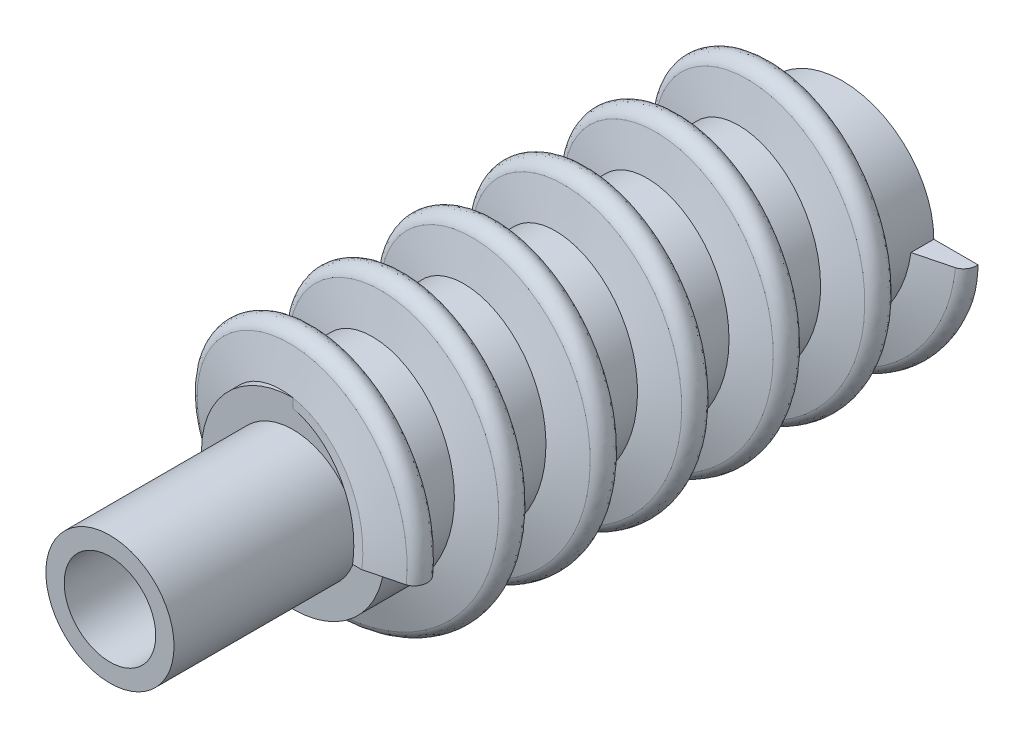
SolidWorks part; units mm, degrees
ref_plane "Front Plane" through (0, 0, 0) normal (0, 0, 1) x (1, 0, 0)
ref_plane "Top Plane" through (0, 0, 0) normal (0, 1, 0) x (1, 0, 0)
ref_plane "Right Plane" through (0, 0, 0) normal (1, 0, 0) x (0, 0, -1)
sketch "Sketch1" plane through (0, 0, 0) normal (0, 0, 1) x (1, 0, 0)
  circle A0 centre (0, 0) radius 5
  dimension "D1" = 10
extrude "Boss-Extrude1" add sketch "Sketch1" along normal blind 30
sketch "Sketch2" plane through (0, 0, 30) normal (0, 0, 1) x (1, 0, 0)
  circle A0 centre (0, 0) radius 3.5
  circle A1 centre (0, 0) radius 2.5
  dimension "D1" = 1
extrude "Boss-Extrude2" add sketch "Sketch2" along normal blind 10
sketch "Sketch5" plane through (0, 0, 0) normal (0, 0, 1) x (1, 0, 0)
  circle A0 centre (0, 0) radius 5 construction
  circle A1 centre (0, 0) radius 5
curve "Helix/Spiral1" pitch 5 height 30 radius 5 left hand yes centre (0, 0, 0) axis (0, 0, 1) start towards (1, 0, 0)
sketch "Sketch7" plane through (0, 0, 0) normal (1, 0, 0) x (0, 0, -1)
  line L12 (0, 5) -> (-30, 5) construction
  line L13 (-27.5, 5) -> (-27.5, 4.5)
  line L15 (-27.5, 4.5) -> (-30, 4.5)
  line L16 (-30, 5) -> (-30, -5) construction
  line L17 (-30, 4.5) -> (-30, 5)
  line L19 (-27.5, 5) -> (-28.1504, 6.8913)
  line L21 (-29.5038, 6.9375) -> (-30, 5)
  arc A1 (-29.5038, 6.9375) -> (-28.1504, 6.8913) centre (-28.8341, 6.7107) cw
  dimension "D1" = 2.5
  dimension "D2" = 0.5
sweep "Sweep2" add profiles "Sketch7" path "Helix/Spiral1"
sketch "Sketch36" plane through (0, 0, 0) normal (0, 1, 0) x (1, 0, 0)
  line L0 (11.1386, 0) -> (-5, 0)
  line L4 (11.1386, 0) -> (11.1386, 1.4522)
  line L6 (-5, 0) -> (-5, 1.4522)
  line L7 (-5, 1.4522) -> (11.1386, 1.4522)
  line L8 (11.1386, 0) -> (11.1386, 1.4522)
extrude "Cut-Extrude2" cut sketch "Sketch36" against normal blind 16 contours L7 L6 L0 L4 region at (3.0693, 0, -0.7261)
